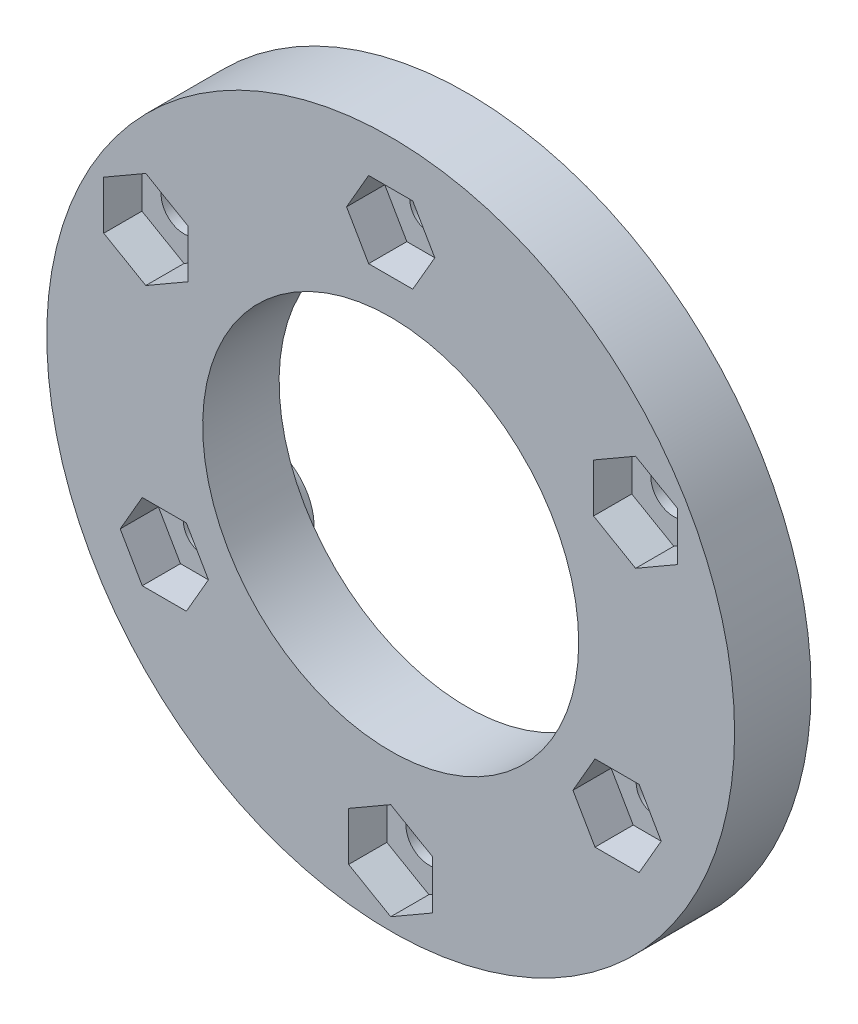
SolidWorks part; units mm, degrees
material "ABS"
ref_plane "Front Plane" through (0, 0, 0) normal (0, 0, 1) x (1, 0, 0)
ref_plane "Top Plane" through (0, 0, 0) normal (0, 1, 0) x (1, 0, 0)
ref_plane "Right Plane" through (0, 0, 0) normal (1, 0, 0) x (0, 0, -1)
sketch "Sketch2" plane through (0, 0, 0) normal (0, 0, 1) x (1, 0, 0)
  line L0 (0, 17.1) -> (0, 0) construction
  line L1 (0, 0) -> (16.0215, 9.25) construction
  circle A0 centre (0, 0) radius 22.5
  circle A1 centre (0, 0) radius 12.3
  circle A2 centre (0, 0) radius 17.1 construction
  circle A3 centre (0, 17.1) radius 1.25
  circle A4 centre (0, 0) radius 18.5 construction
  circle A5 centre (14.809, -8.55) radius 1.25
  circle A8 centre (16.0215, 9.25) radius 1.5
  circle A9 centre (0, -18.5) radius 1.5
  circle A11 centre (0, 0) radius 7.2 construction
  circle A14 centre (0, 17.1) radius 3.3 construction
  circle A15 centre (0, 0) radius 13.8 construction
  circle A20 centre (-14.809, -8.55) radius 1.25
  circle A21 centre (-16.0215, 9.25) radius 1.5
  point P17 (0, 0)
  point P24 (0, 0)
  dimension "D1" = 45
  dimension "D2" = 34.2
  dimension "D4" = 2.5
  dimension "D7" = 3
  dimension "D3" = 14.4
  dimension "D10" = 6.6
  dimension "D5" = 4
  dimension "D9" = 1.5
  dimension "D11" = 60
  dimension "D6" = 3
  dimension "D8" = 3
extrude "Boss-Extrude1" add sketch "Sketch2" along normal blind 5
sketch "Sketch3" plane through (0, 0, 5) normal (0, 0, 1) x (1, 0, 0)
  line L0 (0, 17.1) -> (0, 0) construction
  line L13 (-2.8868, 17.1) -> (-1.4434, 14.6)
  line L14 (-1.4434, 14.6) -> (1.4434, 14.6)
  line L15 (1.4434, 14.6) -> (2.8868, 17.1)
  line L16 (2.8868, 17.1) -> (1.4434, 19.6)
  line L17 (1.4434, 19.6) -> (-1.4434, 19.6)
  line L18 (-1.4434, 19.6) -> (-2.8868, 17.1)
  line L20 (16.0215, 6.0746) -> (18.7715, 7.6623)
  line L21 (18.7715, 7.6623) -> (18.7715, 10.8377)
  line L22 (18.7715, 10.8377) -> (16.0215, 12.4254)
  line L23 (16.0215, 12.4254) -> (13.2715, 10.8377)
  line L24 (13.2715, 10.8377) -> (13.2715, 7.6623)
  line L25 (13.2715, 7.6623) -> (16.0215, 6.0746)
  circle A0 centre (0, 17.1) radius 2.5 construction
  circle A1 centre (16.0215, 9.25) radius 2.75 construction
  dimension "D2" = 5.5
extrude "Cut-Extrude1" cut sketch "Sketch3" against normal blind 2.5
pattern_circular "CirPattern1" count 3 over 360 about axis through (0, 0, 5) along (0, 0, -1) of "Cut-Extrude1" reverse direction yes
sketch "Sketch4" plane through (0, 0, 0) normal (0, 0, -1) x (-1, 0, 0)
  circle A0 centre (0, 17.1) radius 2.5
  circle A1 centre (0, 17.1) radius 3.3
  dimension "D2" = 0.8
extrude "Boss-Extrude2" add sketch "Sketch4" along normal blind 1.5
fillet "Fillet1" radius 1.5 1 edges at (3.3, 17.1, 0)
chamfer "Chamfer1" distance 0.25 angle 45 1 edges at (-2.5, 17.1, -1.5)
pattern_circular "CirPattern2" count 3 over 360 about axis through (0, 0, 5) along (0, 0, -1) of "Fillet1", "Boss-Extrude2", "Chamfer1" reverse direction yes
equation "\"Nr\"= 78"
equation "\"module\"= 0.6"
equation "\"pressure_angle\"= 20.0"
equation "\"h_a\"= 0.6"
equation "\"h_f\"= 0.75"
equation "\"clr_tip_root\"= 0.15000000000000002"
equation "\"dp_r\"= 46.8"
equation "\"db_r\"= 43.97761465278051"
equation "\"fw_r\"= 22.845791438896047"
equation "\"alpha_r\"= 0.8539582918412556"
equation "\"beta_r\"= 4.015608891374819"
equation "\"bearing_ID\"= 45"
equation "\"bearing_OD\"= 58"
equation "\"bearing_height\"= 7"
equation "\"clearance_planet\"= 1.5"
equation "\"case_dist\"= 24.210783717444997"
equation "\"Motor_case_OD_max\"= 88.5"
equation "\"case_mounting_PCD\"= 81.0"
equation "\"bearing mount thickness\"= IIF ( ( \"bearing_OD\" + \"output_mounting_hole_dia\" * 4 ) > ( \"Nr\" * \"module\" + 2 * \"h_b\" ) , \"output_mounting_hole_dia\" * 2 , ( ( \"Nr\" * \"module\" + 2 * \"h_b\" - ( \"bearing_OD\" + \"output_mounting_hole_dia\" * 4 ) ) / 2 ) + \"output_mounting_hole_dia\" * 2 + \"standard_clearance_1_5mm\" )"
equation "\"case_mounting_hole_dia\"= 3"
equation "\"output_mounting_PCD\"= 66"
equation "\"output_mounting_hole_dia\"= 4"
equation "\"clearance_case_mount_holes_shell_thickness\"= 1"
equation "\"motor_case_OD_base\"= 79.0"
equation "\"sec_carrier_thickness\"= 5"
equation "\"sun_coupler_hub_thickness\"= 4"
equation "\"clearance_sun_coupler_sec_carrier\"= 1.5"
equation "\"clearance_motor_and_case\"= 5"
equation "\"motor_OD\"= 64"
equation "\"Motor_case_thickness\"= 2.5"
equation "\"Motor_case_ID\"= 74"
equation "\"case_mounting_hole_shift\"= 1.0"
equation "\"output_mounting_nut_wrench_size\"= 7"
equation "\"output_mounting_nut_thickness\"= 3.2"
equation "\"case_mounting_hole_allen_socket_dia\"= 5.5"
equation "\"output_mounting_nut_depth\"= 3"
equation "\"case_mounting_bolt_depth\"= 4.5"
equation "\"Ns\"= 24"
equation "\"Np_b\"= 33"
equation "\"ring_radial_thickness\"= 7.100000000000001"
equation "\"ring_OD\"= 61.0"
equation "\"ring_to_chamfer_clearance\"= 0.5"
equation "\"Motor_case_OD_base_to_chamfer\"= 5"
equation "\"pattern_offset_from_motor_case_OD_base\"= 3"
equation "\"pattern_bulge_dia\"= 3"
equation "\"pattern_num_bulge\"= 18"
equation "\"pattern_depth\"= 2"
equation "\"motor_height\"= 75"
equation "\"case_mounting_wrench_size\"= 5.5"
equation "\"case_mounting_nut_clearance\"= 2"
equation "\"base_plate_thickness\"= 4"
equation "\"case_mounting_nut_thickness\"= 2.4"
equation "\"case_mounting_surface_height\"= 4"
equation "\"motor_mount_hole_PCD\"= 44"
equation "\"motor_mount_hole_dia\"= 4"
equation "\"motor_mount_hole_num\"= 4"
equation "\"central_hole_offset_from_motor_mount_PCD\"= 5"
equation "\"wire_slot_dist_from_center\"= 22"
equation "\"wire_slot_length\"= 8"
equation "\"wire_slot_radius\"= 2"
equation "\"driver_upper_holes_dist_from_center\"= 29"
equation "\"driver_lower_holes_dist_from_center\"= 13"
equation "\"driver_side_holes_dist_from_center\"= 22.5"
equation "\"driver_mount_holes_dia\"= 3"
equation "\"driver_mount_inserts_OD\"= 4.8"
equation "\"driver_mount_thickness\"= 1.5"
equation "\"driver_mount_height\"= 6"
equation "\"air_flow_hole_offset\"= 3"
equation "\"num_planet\"= 3"
equation "\"planet_pin_bolt_dia\"= 2.5"
equation "\"planet_pin_socket_head_dia\"= 4.5"
equation "\"carrier_PCD\"= 34.199999999999996"
equation "\"D1@Sketch2\"=\"bearing_ID\""
equation "\"D2@Sketch2\"=\"carrier_PCD\""
equation "\"D4@Sketch2\"=\"planet_pin_bolt_dia\""
equation "\"D6@Sketch2\"=\"num_planet\""
equation "\"D8@Sketch2\"=\"num_planet\""
equation "\"D1@CirPattern1\"=\"num_planet\""
equation "\"planet_shaft_dia\"= 5"
equation "\"planet_shaft_step_offset\"= 0.8"
equation "\"carrier_trapezoidal_support_sun_offset\"= 5"
equation "\"carrier_trapezoidal_support_hole_PCD_offset_bearing_ID\"= 4"
equation "\"carrier_trapezoidal_support_hole_dia\"= 3"
equation "\"carrier_trapezoidal_support_hole_socket_head_dia\"= 5.5"
equation "\"carrier_bearing_step_width\"= 1.5"
equation "\"standard_clearance_1_5mm\"= 1.5"
equation "\"standard_fillet_1_5mm\"= 1.5"
equation "\"sun_shaft_bearing_OD\"= 14"
equation "\"sun_shaft_bearing_width\"= 5"
equation "\"standard_bearing_insertion_chamfer\"= 0.5"
equation "\"D7@Sketch2\"=\"carrier_trapezoidal_support_hole_dia\""
equation "\"D5@Sketch2\"=\"carrier_trapezoidal_support_hole_PCD_offset_bearing_ID\""
equation "\"D3@Sketch2\"=\"Ns\"*\"module\""
equation "\"carrier_trapezoidal_support_hole_wrench_size\"= 5.5"
equation "\"planet_pin_bolt_wrench_size\"= 5"
equation "\"D1@Boss-Extrude1\"=\"sec_carrier_thickness\""
equation "\"D1@Cut-Extrude1\"=\"sec_carrier_thickness\"/2"
equation "\"D1@Sketch4\"=\"planet_shaft_dia\""
equation "\"D2@Sketch4\"=\"planet_shaft_step_offset\""
equation "\"D1@Boss-Extrude2\"=\"clearance_planet\""
equation "\"D1@Fillet1\"=\"standard_fillet_1_5mm\""
equation "\"D1@Chamfer1\"=\"standard_bearing_insertion_chamfer\"/2"
equation "\"D1@CirPattern2\"=\"num_planet\""
equation "\"D10@Sketch2\"=\"planet_shaft_dia\"+\"planet_shaft_step_offset\"*2"
equation "\"D9@Sketch2\"=\"standard_clearance_1_5mm\""
equation "\"D1@Sketch3\"=\"planet_pin_bolt_wrench_size\""
equation "\"D11@Sketch2\"=180/\"num_planet\""
equation "\"D2@Sketch3\"=\"carrier_trapezoidal_support_hole_wrench_size\""
equation "\"pressure angle\"= 20.0"
equation "\"h_b\"= 0.75"
equation "\"dp_s\"= 14.399999999999999"
equation "\"db_s\"= 13.53157373931708"
equation "\"fw_s_calc\"= 16.210783717444997"
equation "\"alpha_s\"= 0.8539582918412343"
equation "\"beta_s\"= 5.792083416317531"
equation "\"dp_p_b\"= 19.8"
equation "\"db_p_b\"= 18.605913891560988"
equation "\"fw_p_s\"= 24.345791438896047"
equation "\"alpha_p_b\"= 0.8539582918412414"
equation "\"beta_p_b\"= 3.7466288708629714"
equation "\"planet_bearing_OD\"= 8"
equation "\"planet_bearing_width\"= 2.5"
equation "\"planet_bore\"= 6"
equation "\"motor_output_hole_PCD\"= 32"
equation "\"motor_output_hole_dia\"= 4"
equation "\"motor_output_hole_num\"= 4"
equation "\"sun_shaft_bearing_ID\"= 7"
equation "\"sun_hub_dia\"= 42.0"
equation "\"sun_central_bolt_dia\"= 3"
equation "\"sun_central_bolt_socket_head_dia\"= 5.5"
equation "\"fw_s_used\"= 48.55657515634104"
equation "\"motor_output_hole_CSK_OD\"= 8"
equation "\"motor_output_hole_CSK_head_height\"= 2.0"
equation "\"bearing_retainer_thickness\"= 2"
equation "\"Np_s\"= 21"
equation "\"fw_p_b\"= 16.210783717444997"
equation "\"dp_p_s\"= 12.6"
equation "\"db_p_s\"= 11.840127021902445"
equation "\"alpha_p_s\"= 0.8539582918412556"
equation "\"beta_p_s\"= 6.86351198774606"
equation "\"D1@Fillet2\"=\"standard_fillet_1_5mm\"/3"
